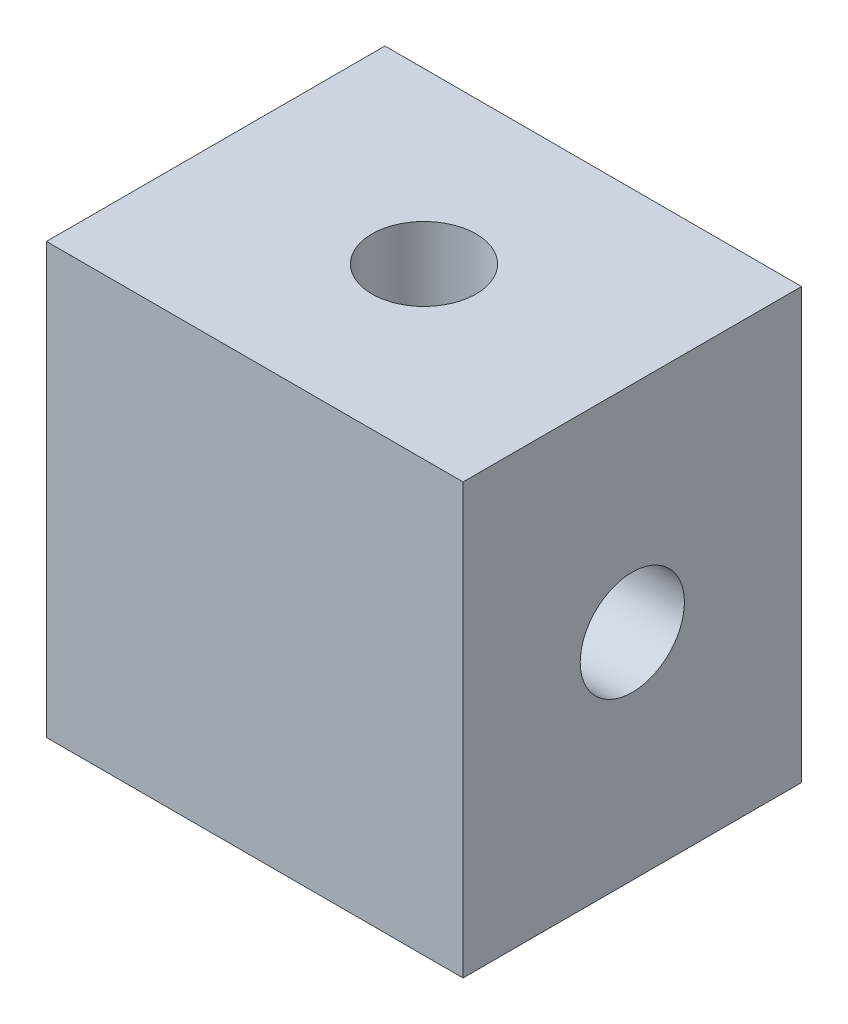
SolidWorks part; units mm, degrees
ref_plane "Front Plane" through (0, 0, 0) normal (0, 0, 1) x (1, 0, 0)
ref_plane "Top Plane" through (0, 0, 0) normal (0, 1, 0) x (1, 0, 0)
ref_plane "Right Plane" through (0, 0, 0) normal (1, 0, 0) x (0, 0, -1)
ref_plane "PL_Block_base" through (0, 0, -13) normal (0, 0, 1) x (1, 0, 0)
sketch "SK_Block" plane through (0, 0, -13) normal (0, 0, 1) x (1, 0, 0)
  line L0 (-16, -16.5) -> (16, -16.5)
  line L1 (16, -16.5) -> (16, 16.5)
  line L2 (16, 16.5) -> (-16, 16.5)
  line L3 (-16, 16.5) -> (-16, -16.5)
  dimension "P1" = 16
  dimension "P2" = 16.5
  dimension "P3" = 16
  dimension "P4" = 16.5
  dimension "P5" = 16
  dimension "P6" = 16.5
  dimension "P7" = 16
  dimension "P8" = 16.5
extrude "Block" add sketch "SK_Block" along normal blind 26
ref_plane "PL_Pitch_Bore_base" through (0, -20, 0) normal (0, 1, 0) x (1, 0, 0)
sketch "SK_Pitch_Bore" plane through (0, -20, 0) normal (0, 1, 0) x (1, 0, 0)
  circle A0 centre (0, 0) radius 4
  dimension "D1_SK_Pitch_Bore" = 8
extrude "Pitch_Bore" cut sketch "SK_Pitch_Bore" along normal blind 40
ref_plane "PL_Roll_Bore_base" through (-20, 0, 0) normal (1, 0, 0) x (0, 0, -1)
sketch "SK_Roll_Bore" plane through (-20, 0, 0) normal (1, 0, 0) x (0, 0, -1)
  circle A0 centre (0, 0) radius 4
  dimension "D1_SK_Roll_Bore" = 8
extrude "Roll_Bore" cut sketch "SK_Roll_Bore" along normal blind 40
ref_axis "AX_Pitch" through (0, 18.15, 0) along (0, -1, 0)
ref_axis "AX_Roll" through (-17.6, 0, 0) along (1, 0, 0)
equation "\"Cross_size\" = 32"
